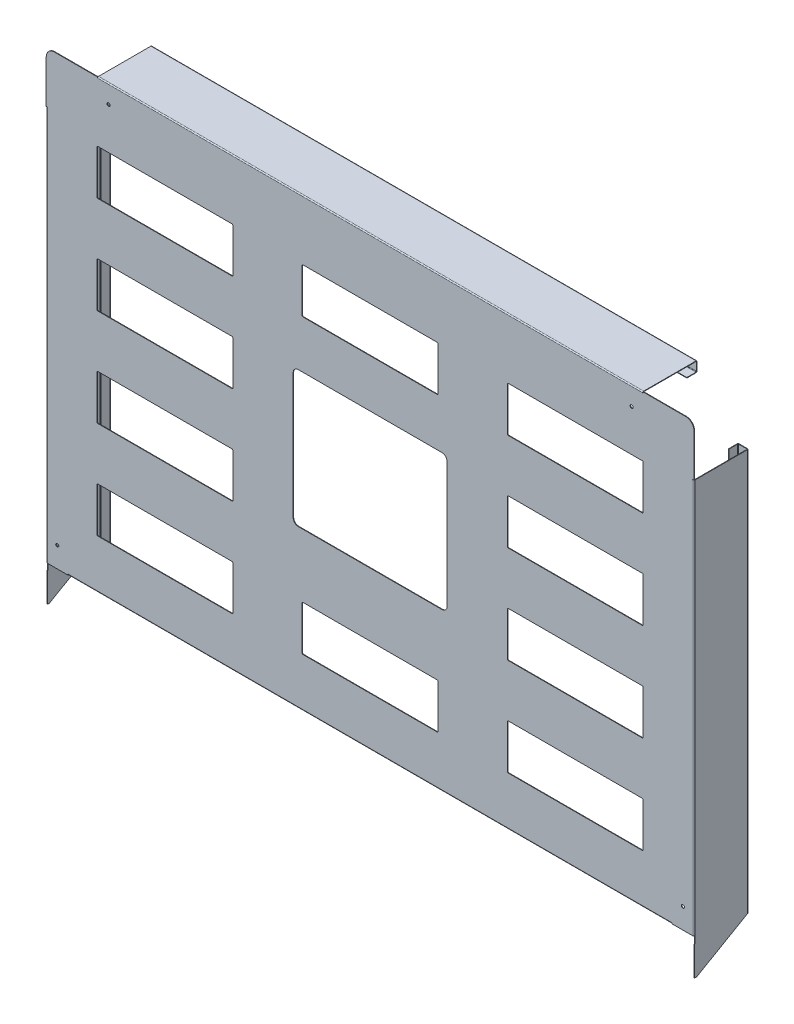
SolidWorks part; units mm, degrees
note: The reader was unsure of these and kept them because the rebuilt part matched: flange length of "Edge-Flange1", "Edge-Flange2", "Edge-Flange3", "Edge-Flange4", "Edge-Flange5", "Edge-Flange6", "Edge-Flange7".
ref_plane "Front Plane" through (0, 0, 0) normal (0, 0, 1) x (1, 0, 0)
ref_plane "Top Plane" through (0, 0, 0) normal (0, 1, 0) x (1, 0, 0)
ref_plane "Right Plane" through (0, 0, 0) normal (1, 0, 0) x (0, 0, -1)
sketch "Sketch1" plane through (0, 0, 0) normal (0, 0, 1) x (1, 0, 0)
  line L1 (0, 0) -> (1263, 0)
  line L2 (0, 0) -> (0, 854)
  line L3 (16, 870) -> (1247, 870)
  line L4 (1263, 0) -> (1263, 854)
  arc A0 (1247, 870) -> (1263, 854) centre (1247, 854) cw
  arc A1 (0, 854) -> (16, 870) centre (16, 854) cw
  dimension "D3" = 16
  dimension "D1" = 1263
  dimension "D2" = 870
base flange "Base-Flange1" sketch "Sketch1" thickness 1 reverse thickness direction no parameters "D1"=1
edge flange "Edge-Flange1" sketch "Sketch8" flange angle 90 flange length 18 flange position material inside bend radius 1 thickness 1 relief rectangular parameters "D6"=10
sketch "Sketch8" plane through (0, 0, -1) normal (0, -1, 0) x (-1, 0, 0)
  line L0 (0, 0) -> (-1263, 0) construction
  line L1 (-43, 0) -> (-1220, 0)
  line L2 (-1220, 0) -> (-1220, 18)
  line L3 (-1220, 18) -> (-43, 18)
  line L4 (-43, 18) -> (-43, 0)
  line L5 (0, 0) -> (0, -1) construction
  line L6 (-1263, 0) -> (-1263, -1) construction
  circle A0 centre (-82, 9) radius 2.75
  circle A1 centre (-262, 9) radius 2.75
  circle A2 centre (-442, 9) radius 2.75
  circle A3 centre (-622, 9) radius 2.75
  circle A4 centre (-802, 9) radius 2.75
  circle A5 centre (-982, 9) radius 2.75
  circle A6 centre (-1162, 9) radius 2.75
  point P6 (-43, 9)
  dimension "D1" = 5.5
  dimension "D2" = 39
  dimension "D4" = 43
  dimension "D5" = 43
  dimension "D3" = 7
bend "EdgeBend1" bend radius 1 bend angle 90 parameters "D5"=1
sketch "Sketch9" plane through (0, 0, 0) normal (0, 0, 1) x (1, 0, 0)
  line L0 (1263, 0) -> (1263, 854) construction
  line L1 (1162, 753) -> (901, 753)
  line L2 (1164, 751) -> (1164, 667)
  line L3 (1162, 665) -> (901, 665)
  line L4 (899, 751) -> (899, 667)
  line L5 (1247, 870) -> (16, 870) construction
  line L6 (764, 751) -> (764, 667)
  line L7 (762, 753) -> (501, 753)
  line L8 (762, 665) -> (501, 665)
  line L9 (499, 751) -> (499, 667)
  line L10 (364, 751) -> (364, 667)
  line L11 (362, 753) -> (101, 753)
  line L12 (362, 665) -> (101, 665)
  line L13 (99, 751) -> (99, 667)
  line L18 (364, 561) -> (364, 477)
  line L19 (362, 563) -> (101, 563)
  line L20 (362, 475) -> (101, 475)
  line L21 (99, 561) -> (99, 477)
  line L26 (364, 371) -> (364, 287)
  line L27 (362, 373) -> (101, 373)
  line L28 (362, 285) -> (101, 285)
  line L29 (99, 371) -> (99, 287)
  line L30 (764, 181) -> (764, 97)
  line L31 (762, 183) -> (501, 183)
  line L32 (762, 95) -> (501, 95)
  line L33 (499, 181) -> (499, 97)
  line L34 (364, 181) -> (364, 97)
  line L35 (362, 183) -> (101, 183)
  line L36 (362, 95) -> (101, 95)
  line L37 (99, 181) -> (99, 97)
  line L38 (1164, 561) -> (1164, 477)
  line L39 (1162, 563) -> (901, 563)
  line L40 (1162, 475) -> (901, 475)
  line L41 (899, 561) -> (899, 477)
  line L42 (1164, 371) -> (1164, 287)
  line L43 (1162, 373) -> (901, 373)
  line L44 (1162, 285) -> (901, 285)
  line L45 (899, 371) -> (899, 287)
  line L46 (1164, 181) -> (1164, 97)
  line L47 (1162, 183) -> (901, 183)
  line L48 (1162, 95) -> (901, 95)
  line L49 (899, 181) -> (899, 97)
  line L50 (764, 371) -> (764, 287) [skipped]
  line L51 (764, 561) -> (764, 477) [skipped]
  line L52 (762, 563) -> (501, 563) [skipped]
  line L53 (762, 475) -> (501, 475) [skipped]
  line L54 (499, 561) -> (499, 477) [skipped]
  line L55 (762, 373) -> (501, 373) [skipped]
  line L56 (762, 285) -> (501, 285) [skipped]
  line L57 (499, 371) -> (499, 287) [skipped]
  arc A0 (1164, 667) -> (1162, 665) centre (1162, 667) cw
  arc A1 (901, 665) -> (899, 667) centre (901, 667) cw
  arc A2 (901, 753) -> (899, 751) centre (901, 751) ccw
  arc A3 (1162, 753) -> (1164, 751) centre (1162, 751) cw
  arc A4 (762, 753) -> (764, 751) centre (762, 751) cw
  arc A5 (764, 667) -> (762, 665) centre (762, 667) cw
  arc A6 (501, 665) -> (499, 667) centre (501, 667) cw
  arc A7 (501, 753) -> (499, 751) centre (501, 751) ccw
  arc A8 (362, 753) -> (364, 751) centre (362, 751) cw
  arc A9 (364, 667) -> (362, 665) centre (362, 667) cw
  arc A10 (101, 665) -> (99, 667) centre (101, 667) cw
  arc A11 (101, 753) -> (99, 751) centre (101, 751) ccw
  arc A16 (362, 563) -> (364, 561) centre (362, 561) cw
  arc A17 (364, 477) -> (362, 475) centre (362, 477) cw
  arc A18 (101, 475) -> (99, 477) centre (101, 477) cw
  arc A19 (101, 563) -> (99, 561) centre (101, 561) ccw
  arc A24 (362, 373) -> (364, 371) centre (362, 371) cw
  arc A25 (364, 287) -> (362, 285) centre (362, 287) cw
  arc A26 (101, 285) -> (99, 287) centre (101, 287) cw
  arc A27 (101, 373) -> (99, 371) centre (101, 371) ccw
  arc A28 (762, 183) -> (764, 181) centre (762, 181) cw
  arc A29 (764, 97) -> (762, 95) centre (762, 97) cw
  arc A30 (501, 95) -> (499, 97) centre (501, 97) cw
  arc A31 (501, 183) -> (499, 181) centre (501, 181) ccw
  arc A32 (362, 183) -> (364, 181) centre (362, 181) cw
  arc A33 (364, 97) -> (362, 95) centre (362, 97) cw
  arc A34 (101, 95) -> (99, 97) centre (101, 97) cw
  arc A35 (101, 183) -> (99, 181) centre (101, 181) ccw
  arc A36 (1162, 563) -> (1164, 561) centre (1162, 561) cw
  arc A37 (1164, 477) -> (1162, 475) centre (1162, 477) cw
  arc A38 (901, 475) -> (899, 477) centre (901, 477) cw
  arc A39 (901, 563) -> (899, 561) centre (901, 561) ccw
  arc A40 (1162, 373) -> (1164, 371) centre (1162, 371) cw
  arc A41 (1164, 287) -> (1162, 285) centre (1162, 287) cw
  arc A42 (901, 285) -> (899, 287) centre (901, 287) cw
  arc A43 (901, 373) -> (899, 371) centre (901, 371) ccw
  arc A44 (1162, 183) -> (1164, 181) centre (1162, 181) cw
  arc A45 (1164, 97) -> (1162, 95) centre (1162, 97) cw
  arc A46 (901, 95) -> (899, 97) centre (901, 97) cw
  arc A47 (901, 183) -> (899, 181) centre (901, 181) ccw
  arc A48 (764, 477) -> (762, 475) centre (762, 477) cw [skipped]
  arc A49 (501, 475) -> (499, 477) centre (501, 477) cw [skipped]
  arc A50 (762, 373) -> (764, 371) centre (762, 371) cw [skipped]
  arc A51 (764, 287) -> (762, 285) centre (762, 287) cw [skipped]
  arc A52 (501, 285) -> (499, 287) centre (501, 287) cw [skipped]
  arc A53 (501, 373) -> (499, 371) centre (501, 371) ccw [skipped]
  arc A54 (762, 563) -> (764, 561) centre (762, 561) cw [skipped]
  arc A55 (501, 563) -> (499, 561) centre (501, 561) ccw [skipped]
  dimension "D5" = 2
  dimension "D1" = 99
  dimension "D2" = 265
  dimension "D3" = 88
  dimension "D4" = 117
  dimension "D6" = 3
  dimension "D7" = 4
extrude "Cut-Extrude1" cut sketch "Sketch9" against normal blind 10 normal cut yes
sketch "Sketch10" plane through (0, 0, 0) normal (0, 0, 1) x (1, 0, 0)
  line L1 (491.5, 306.5) -> (771.5, 306.5)
  line L2 (481.5, 316.5) -> (481.5, 561.5)
  line L3 (491.5, 571.5) -> (771.5, 571.5)
  line L4 (781.5, 316.5) -> (781.5, 561.5)
  line L8 (1247, 870) -> (16, 870) construction
  arc A0 (491.5, 306.5) -> (481.5, 316.5) centre (491.5, 316.5) cw
  arc A1 (771.5, 306.5) -> (781.5, 316.5) centre (771.5, 316.5) ccw
  arc A2 (481.5, 561.5) -> (491.5, 571.5) centre (491.5, 561.5) cw
  arc A3 (771.5, 571.5) -> (781.5, 561.5) centre (771.5, 561.5) cw
  point P8 (631.5, 571.5)
  point P9 (631.5, 870)
  dimension "D5" = 10
  dimension "D1" = 300
  dimension "D2" = 265
  dimension "D3" = 298.5
extrude "Cut-Extrude2" cut sketch "Sketch10" against normal blind 10 normal cut yes
sketch "Sketch11" plane through (0, 0, -1) normal (0, 0, -1) x (-1, 0, 0)
  line L0 (-762.2929, 578.3623) -> (-474.7071, 578.3623) construction
  line L1 (-762.2929, 578.3623) -> (-474.7071, 578.3623) construction
  line L2 (-455.5, 559.4244) -> (-455.5, 302.3841) construction
  line L3 (-474.7071, 282.858) -> (-762.2929, 282.858) construction
  line L4 (-781.5, 302.8243) -> (-781.5, 559.4244) construction
  line L5 (-781.5, 302.3841) -> (-781.5, 559.4244) construction
  ellipse E0 centre (-474.7071, 576.3964) end of major axis (-472.7071, 576.3964) minor radius 1.9659 (-472.7071, 576.3964) -> (-474.7071, 578.3623) ccw construction
edge flange "Edge-Flange2" sketch "Sketch14" flange angle 90 flange length 104 flange position material inside bend radius 1 thickness 1 relief rectangular parameters "D6"=10
sketch "Sketch14" plane through (0, 870, -1) normal (0, 1, 0) x (1, 0, 0)
  line L0 (1247, 0) -> (16, 0) construction
  line L1 (1163, 0) -> (100, 0)
  line L2 (100, 0) -> (100, 103)
  line L3 (100, 103) -> (1163, 103)
  line L4 (1163, 103) -> (1163, 0)
  line L5 (1263, 0) -> (1263, -1) construction
  line L6 (0, 0) -> (0, -1) construction
  dimension "D1" = 100
  dimension "D2" = 100
  dimension "D3" = 103
bend "EdgeBend2" bend radius 1 bend angle 90 parameters "D5"=2
edge flange "Edge-Flange3" sketch "Sketch19" flange angle 90 flange length 104 flange position material inside bend radius 1 thickness 1 relief rectangular parameters "D6"=10
sketch "Sketch19" plane through (1263, 0, -1) normal (1, 0, 0) x (0, -1, 0)
  line L0 (0, 0) -> (-854, 0) construction
  line L1 (13.7, 0) -> (-770, 0)
  line L2 (-770, 0) -> (-770, 103)
  line L3 (-770, 103) -> (13.7, 103)
  line L4 (13.7, 103) -> (13.7, 0)
  line L5 (-870, 1) -> (-870, 103) construction
  dimension "D1" = 100
  dimension "D2" = 103
  dimension "D3" = 13.7
bend "EdgeBend3" bend radius 1 bend angle 90 parameters "D5"=3
edge flange "Edge-Flange4" sketch "Sketch22" flange angle 90 flange length 18 flange position bend outside bend radius 1 thickness 1 relief rectangular parameters "D6"=10
sketch "Sketch22" plane through (0, 869, -104) normal (0, 0, -1) x (1, 0, 0)
  line L0 (1163, 0) -> (100, 0) construction
  line L1 (1163, 0) -> (100, 0)
  line L2 (100, 0) -> (100, 17)
  line L3 (100, 17) -> (1163, 17)
  line L4 (1163, 17) -> (1163, 0)
bend "EdgeBend4" bend radius 1 bend angle 90 parameters "D5"=4
edge flange "Edge-Flange5" sketch "Sketch25" flange angle 90 flange length 20 flange position bend outside bend radius 1 thickness 1 relief rectangular parameters "D6"=10
sketch "Sketch25" plane through (0, 852, -105) normal (0, 1, 0) x (-1, 0, 0)
  line L2 (-1163, 0) -> (-1163, 19)
  line L3 (-1163, 19) -> (-100, 19)
  line L4 (-100, 19) -> (-100, 0)
  line L5 (-100, 0) -> (-1163, 0) construction
  line L6 (-100, 0) -> (-1163, 0)
bend "EdgeBend5" bend radius 1 bend angle 90 parameters "D5"=5
edge flange "Edge-Flange6" sketch "Sketch28" flange angle 90 flange length 18 flange position bend outside bend radius 1 thickness 1 relief rectangular parameters "D6"=10
sketch "Sketch28" plane through (1262, 0, -104) normal (0, 0, -1) x (0, -1, 0)
  line L0 (13.7, 0) -> (-770, 0) construction
  line L1 (13.7, 0) -> (-770, 0)
  line L2 (-770, 0) -> (-770, 17)
  line L3 (-770, 17) -> (13.7, 17)
  line L4 (13.7, 17) -> (13.7, 0)
bend "EdgeBend6" bend radius 1 bend angle 90 parameters "D5"=6
edge flange "Edge-Flange7" sketch "Sketch31" flange angle 90 flange length 19 flange position bend outside bend radius 1 thickness 1 relief rectangular parameters "D6"=10
sketch "Sketch31" plane through (1245, 0, -105) normal (1, 0, 0) x (0, 1, 0)
  line L2 (-13.7, 0) -> (-13.7, 18)
  line L3 (-13.7, 18) -> (770, 18)
  line L4 (770, 18) -> (770, 0)
  line L9 (770, 0) -> (-13.7, 0) construction
  line L10 (770, 0) -> (-13.7, 0)
bend "EdgeBend7" bend radius 1 bend angle 90 parameters "D5"=7
ref_plane "Plane1" through (631.5, 0, 0) normal (1, 0, 0) x (0, 0, -1)
mirror "Mirror1" about plane through (631.5, 0, 0) normal (1, 0, 0) of "Edge-Flange3", "Edge-Flange6", "Edge-Flange7"
bend "MirrorBend1" bend radius 1 bend angle 90 parameters "D5"=8
bend "MirrorBend2" bend radius 1 bend angle 90 parameters "D5"=9
bend "MirrorBend3" bend radius 1 bend angle 90 parameters "D5"=10
sketch "Sketch32" plane through (1263, 0, 0) normal (1, 0, 0) x (0, 0, -1)
  line L1 (5.5055, -70.5658) -> (104, -13.7)
  line L2 (104, -13.7) -> (1, -13.7)
  line L4 (1, -13.7) -> (1, -70.1998)
  line L5 (1.5, -70.6998) -> (5.0055, -70.6998)
  line L7 (2, -13.7) -> (2, 0) construction
  arc A0 (5.0055, -70.6998) -> (5.5055, -70.5658) centre (5.0055, -69.6998) ccw
  arc A1 (1, -70.1998) -> (1.5, -70.6998) centre (1.5, -70.1998) ccw
  point P12 (5.2734, -70.6998)
  dimension "D4" = 1
  dimension "D5" = 0.5
  dimension "D1" = 30
  dimension "D2" = 1
base flange "Tab1" sketch "Sketch32" thickness 1 reverse thickness direction no parameters "D1"=1
ref_plane "Plane2" through (631.5, 0, 0) normal (1, 0, 0) x (0, 0, -1)
mirror "Mirror2" about plane through (631.5, 0, 0) normal (1, 0, 0) of "Tab1"
sketch "Sketch33" plane through (0, 0, 0) normal (0, 0, 1) x (1, 0, 0)
  line L0 (631.5, 868) -> (631.5, 781.3325) construction
  line L1 (1163, 868) -> (100, 868) construction
  line L2 (99.5, 870) -> (16, 870) construction
  line L3 (0, 854) -> (0, 770.5) construction
  line L4 (2, 0) -> (42.5, 0) construction
  line L5 (0, 770) -> (0, 0) construction
  circle A0 centre (121.5, 834) radius 3
  circle A1 centre (1141.5, 834) radius 3
  circle A2 centre (21.5, 40) radius 3
  circle A3 centre (1241.5, 40) radius 3
  dimension "D1" = 6
  dimension "D3" = 121.5
  dimension "D4" = 6
  dimension "D5" = 40
  dimension "D6" = 21.5
  dimension "D2" = 36
extrude "Cut-Extrude3" cut sketch "Sketch33" against normal blind 10 normal cut yes
sketch "Bend-Lines1" [suppressed] plane through (0, 0, 0) normal (0, 1, 0) x (1, 0, 0)
sketch "Bounding-Box1" [suppressed] plane through (0, 0, 0) normal (0, 1, 0) x (1, 0, 0)
sheet metal parameters "Sheet-Metal1" thickness 1 parameters "D1"=2
flat pattern "Flat-Pattern1" [suppressed]
sketch "Bend-Lines2" plane through (0, 0, 0) normal (0, 1, 0) x (1, 0, 0)
sketch3d "Bounding-Box2" [suppressed]
  line L0 (15, 15, 0) -> (-1227, 15, 0) construction
  line L1 (15, -935, 0) -> (-1227, -935, 0) construction
  line L2 (15, 15, 0) -> (15, -935, 0) construction
  line L3 (-1227, 15, 0) -> (-1227, -935, 0) construction
sheet metal parameters "Sheet-Metal2" thickness 1 parameters "D1"=2
flat pattern "Flat-Pattern1"
sketch "Bend-Lines2" plane through (0, 0, 0) normal (0, 0, 1) x (1, 0, 0)
  line L0 (0, 0.8219) -> (1242, 0.8219) construction
  line L1 (0, 0.8219) -> (1242, 0.8219) construction
sketch3d "Bounding-Box2" [suppressed]
  line L0 (-15, 15, 0) -> (1227, 15, 0) construction
  line L1 (-15, -946.3562, 0) -> (1227, -946.3562, 0) construction
  line L2 (-15, 15, 0) -> (-15, -946.3562, 0) construction
  line L3 (1227, 15, 0) -> (1227, -946.3562, 0) construction
bend of the flat pattern "Flatten-<EdgeBend1>1"
sheet metal parameters "Sheet-Metal3" thickness 1 parameters "D1"=2
flat pattern "Flat-Pattern1"
sketch "Bend-Lines2" plane through (0, 0, 0) normal (0, 0, 1) x (1, 0, 0)
  line L0 (0, 0.8219) -> (1244, 0.8219) construction
  line L1 (0, 0.8219) -> (1244, 0.8219) construction
sketch3d "Bounding-Box2" [suppressed]
  line L0 (-16, 16, 0) -> (1228, 16, 0) construction
  line L1 (-16, -945.3562, 0) -> (1228, -945.3562, 0) construction
  line L2 (-16, 16, 0) -> (-16, -945.3562, 0) construction
  line L3 (1228, 16, 0) -> (1228, -945.3562, 0) construction
bend of the flat pattern "Flatten-<EdgeBend1>1"
sheet metal parameters "Sheet-Metal4" thickness 1 parameters "D1"=2
flat pattern "Flat-Pattern1"
sketch "Bend-Lines2" plane through (0, 0, 0) normal (0, 0, 1) x (1, 0, 0)
  line L0 (43, 0.8219) -> (1201, 0.8219) construction
  line L1 (43, 0.8219) -> (1201, 0.8219) construction
sketch3d "Bounding-Box2" [suppressed]
  line L0 (-16, 16, 0) -> (1228, 16, 0) construction
  line L1 (-16, -861.3562, 0) -> (1228, -861.3562, 0) construction
  line L2 (-16, 16, 0) -> (-16, -861.3562, 0) construction
  line L3 (1228, 16, 0) -> (1228, -861.3562, 0) construction
bend of the flat pattern "Flatten-<EdgeBend1>1"
sheet metal parameters "Sheet-Metal5" thickness 1 parameters "D1"=2
flat pattern "Flat-Pattern1"
sketch "Bend-Lines2" plane through (0, 0, 0) normal (0, 0, 1) x (1, 0, 0)
  line L0 (43, 0.8219) -> (1201, 0.8219) construction
  line L1 (43, 0.8219) -> (1201, 0.8219) construction
  line L2 (1144, 861.1781) -> (100, 861.1781) construction
  line L3 (1144, 861.1781) -> (100, 861.1781) construction
sketch3d "Bounding-Box2" [suppressed]
  line L0 (-16, 117.3562, 0) -> (1228, 117.3562, 0) construction
  line L1 (-16, -861.3562, 0) -> (1228, -861.3562, 0) construction
  line L2 (-16, 117.3562, 0) -> (-16, -861.3562, 0) construction
  line L3 (1228, 117.3562, 0) -> (1228, -861.3562, 0) construction
bend of the flat pattern "Flatten-<EdgeBend1>1"
bend of the flat pattern "Flatten-<EdgeBend2>1"
sheet metal parameters "Sheet-Metal6" thickness 1 parameters "D1"=2
flat pattern "Flat-Pattern1"
sketch "Bend-Lines2" plane through (0, 0, 0) normal (0, 0, 1) x (1, 0, 0)
  line L0 (43, 0.8219) -> (1201, 0.8219) construction
  line L1 (43, 0.8219) -> (1201, 0.8219) construction
  line L2 (1144, 861.1781) -> (100, 861.1781) construction
  line L3 (1144, 861.1781) -> (100, 861.1781) construction
  line L4 (1245.1781, 0) -> (1245.1781, 762) construction
  line L5 (1245.1781, 0) -> (1245.1781, 762) construction
sketch3d "Bounding-Box2" [suppressed]
  line L0 (-16, 117.3562, 0) -> (1329.3562, 117.3562, 0) construction
  line L1 (-16, -861.3562, 0) -> (1329.3562, -861.3562, 0) construction
  line L2 (-16, 117.3562, 0) -> (-16, -861.3562, 0) construction
  line L3 (1329.3562, 117.3562, 0) -> (1329.3562, -861.3562, 0) construction
bend of the flat pattern "Flatten-<EdgeBend1>1"
bend of the flat pattern "Flatten-<EdgeBend2>1"
bend of the flat pattern "Flatten-<EdgeBend3>1"
sheet metal parameters "Sheet-Metal7" thickness 1 parameters "D1"=2
flat pattern "Flat-Pattern1"
sketch "Bend-Lines2" plane through (0, 0, 0) normal (0, 0, 1) x (1, 0, 0)
  line L0 (43, 0.8219) -> (1201, 0.8219) construction
  line L1 (43, 0.8219) -> (1201, 0.8219) construction
  line L2 (1144, 861.1781) -> (100, 861.1781) construction
  line L3 (1144, 861.1781) -> (100, 861.1781) construction
  line L4 (1245.1781, 0) -> (1245.1781, 762) construction
  line L5 (1245.1781, 0) -> (1245.1781, 762) construction
  line L6 (1144, 962.5343) -> (100, 962.5343) construction
  line L7 (1144, 962.5343) -> (100, 962.5343) construction
sketch3d "Bounding-Box2" [suppressed]
  line L0 (-16, 135.7124, 0) -> (1329.3562, 135.7124, 0) construction
  line L1 (-16, -861.3562, 0) -> (1329.3562, -861.3562, 0) construction
  line L2 (-16, 135.7124, 0) -> (-16, -861.3562, 0) construction
  line L3 (1329.3562, 135.7124, 0) -> (1329.3562, -861.3562, 0) construction
bend of the flat pattern "Flatten-<EdgeBend1>1"
bend of the flat pattern "Flatten-<EdgeBend2>1"
bend of the flat pattern "Flatten-<EdgeBend3>1"
bend of the flat pattern "Flatten-<EdgeBend4>1"
sheet metal parameters "Sheet-Metal8" thickness 1 parameters "D1"=2
flat pattern "Flat-Pattern1"
sketch "Bend-Lines2" plane through (0, 0, 0) normal (0, 0, 1) x (1, 0, 0)
  line L0 (43, 0.8219) -> (1201, 0.8219) construction
  line L1 (43, 0.8219) -> (1201, 0.8219) construction
  line L2 (1144, 861.1781) -> (100, 861.1781) construction
  line L3 (1144, 861.1781) -> (100, 861.1781) construction
  line L4 (1245.1781, 0) -> (1245.1781, 762) construction
  line L5 (1245.1781, 0) -> (1245.1781, 762) construction
  line L6 (1144, 962.5343) -> (100, 962.5343) construction
  line L7 (1144, 962.5343) -> (100, 962.5343) construction
  line L8 (1144, 980.8905) -> (100, 980.8905) construction
  line L9 (1144, 980.8905) -> (100, 980.8905) construction
sketch3d "Bounding-Box2" [suppressed]
  line L0 (-16, 156.0686, 0) -> (1329.3562, 156.0686, 0) construction
  line L1 (-16, -861.3562, 0) -> (1329.3562, -861.3562, 0) construction
  line L2 (-16, 156.0686, 0) -> (-16, -861.3562, 0) construction
  line L3 (1329.3562, 156.0686, 0) -> (1329.3562, -861.3562, 0) construction
bend of the flat pattern "Flatten-<EdgeBend1>1"
bend of the flat pattern "Flatten-<EdgeBend2>1"
bend of the flat pattern "Flatten-<EdgeBend3>1"
bend of the flat pattern "Flatten-<EdgeBend4>1"
bend of the flat pattern "Flatten-<EdgeBend5>1"
sheet metal parameters "Sheet-Metal9" thickness 1 parameters "D1"=2
flat pattern "Flat-Pattern1"
sketch "Bend-Lines2" plane through (0, 0, 0) normal (0, 0, 1) x (1, 0, 0)
  line L0 (43, 0.8219) -> (1201, 0.8219) construction
  line L1 (43, 0.8219) -> (1201, 0.8219) construction
  line L2 (1144, 861.1781) -> (100, 861.1781) construction
  line L3 (1144, 861.1781) -> (100, 861.1781) construction
  line L4 (1245.1781, 0) -> (1245.1781, 762) construction
  line L5 (1245.1781, 0) -> (1245.1781, 762) construction
  line L6 (1144, 962.5343) -> (100, 962.5343) construction
  line L7 (1144, 962.5343) -> (100, 962.5343) construction
  line L8 (1144, 980.8905) -> (100, 980.8905) construction
  line L9 (1144, 980.8905) -> (100, 980.8905) construction
  line L10 (1346.5343, 0) -> (1346.5343, 762) construction
  line L11 (1346.5343, 0) -> (1346.5343, 762) construction
sketch3d "Bounding-Box2" [suppressed]
  line L0 (-16, 156.0686, 0) -> (1347.7124, 156.0686, 0) construction
  line L1 (-16, -861.3562, 0) -> (1347.7124, -861.3562, 0) construction
  line L2 (-16, 156.0686, 0) -> (-16, -861.3562, 0) construction
  line L3 (1347.7124, 156.0686, 0) -> (1347.7124, -861.3562, 0) construction
bend of the flat pattern "Flatten-<EdgeBend1>1"
bend of the flat pattern "Flatten-<EdgeBend2>1"
bend of the flat pattern "Flatten-<EdgeBend3>1"
bend of the flat pattern "Flatten-<EdgeBend4>1"
bend of the flat pattern "Flatten-<EdgeBend5>1"
bend of the flat pattern "Flatten-<EdgeBend6>1"
sheet metal parameters "Sheet-Metal10" thickness 1 parameters "D1"=2
flat pattern "Flat-Pattern1"
sketch "Bend-Lines2" plane through (0, 0, 0) normal (0, 0, 1) x (1, 0, 0)
  line L0 (43, 0.8219) -> (1201, 0.8219) construction
  line L1 (43, 0.8219) -> (1201, 0.8219) construction
  line L2 (1144, 861.1781) -> (100, 861.1781) construction
  line L3 (1144, 861.1781) -> (100, 861.1781) construction
  line L4 (1245.1781, 0) -> (1245.1781, 762) construction
  line L5 (1245.1781, 0) -> (1245.1781, 762) construction
  line L6 (1144, 962.5343) -> (100, 962.5343) construction
  line L7 (1144, 962.5343) -> (100, 962.5343) construction
  line L8 (1144, 980.8905) -> (100, 980.8905) construction
  line L9 (1144, 980.8905) -> (100, 980.8905) construction
  line L10 (1346.5343, 0) -> (1346.5343, 762) construction
  line L11 (1346.5343, 0) -> (1346.5343, 762) construction
  line L12 (1364.8905, 0) -> (1364.8905, 762) construction
  line L13 (1364.8905, 0) -> (1364.8905, 762) construction
sketch3d "Bounding-Box2" [suppressed]
  line L0 (-16, 156.0686, 0) -> (1368.0686, 156.0686, 0) construction
  line L1 (-16, -861.3562, 0) -> (1368.0686, -861.3562, 0) construction
  line L2 (-16, 156.0686, 0) -> (-16, -861.3562, 0) construction
  line L3 (1368.0686, 156.0686, 0) -> (1368.0686, -861.3562, 0) construction
bend of the flat pattern "Flatten-<EdgeBend1>1"
bend of the flat pattern "Flatten-<EdgeBend2>1"
bend of the flat pattern "Flatten-<EdgeBend3>1"
bend of the flat pattern "Flatten-<EdgeBend4>1"
bend of the flat pattern "Flatten-<EdgeBend5>1"
bend of the flat pattern "Flatten-<EdgeBend6>1"
bend of the flat pattern "Flatten-<EdgeBend7>1"
sheet metal parameters "Sheet-Metal11" thickness 1 parameters "D1"=2
flat pattern "Flat-Pattern1"
sketch "Bend-Lines2" plane through (0, 0, 0) normal (0, 0, 1) x (1, 0, 0)
  line L0 (43, 0.8219) -> (1220, 0.8219) construction
  line L1 (43, 0.8219) -> (1220, 0.8219) construction
  line L2 (1163, 869.1781) -> (100, 869.1781) construction
  line L3 (1163, 869.1781) -> (100, 869.1781) construction
  line L4 (1262.1781, 0) -> (1262.1781, 770) construction
  line L5 (1262.1781, 0) -> (1262.1781, 770) construction
  line L6 (1163, 973.5343) -> (100, 973.5343) construction
  line L7 (1163, 973.5343) -> (100, 973.5343) construction
  line L8 (1163, 991.8905) -> (100, 991.8905) construction
  line L9 (1163, 991.8905) -> (100, 991.8905) construction
  line L10 (1366.5343, 0) -> (1366.5343, 770) construction
  line L11 (1366.5343, 0) -> (1366.5343, 770) construction
  line L12 (1384.8905, 0) -> (1384.8905, 770) construction
  line L13 (1384.8905, 0) -> (1384.8905, 770) construction
  line L14 (-121.8905, 770) -> (-121.8905, 0) construction
  line L15 (-103.5343, 770) -> (-103.5343, 0) construction
  line L16 (0.8219, 770) -> (0.8219, 0) construction
  line L17 (-121.8905, 770) -> (-121.8905, 0) construction
  line L18 (-103.5343, 770) -> (-103.5343, 0) construction
  line L19 (0.8219, 770) -> (0.8219, 0) construction
sketch3d "Bounding-Box2" [suppressed]
  line L0 (-157.0686, -871.3562, 0) -> (1388.0686, -871.3562, 0) construction
  line L1 (-157.0686, 157.0686, 0) -> (1388.0686, 157.0686, 0) construction
  line L2 (-157.0686, -871.3562, 0) -> (-157.0686, 157.0686, 0) construction
  line L3 (1388.0686, -871.3562, 0) -> (1388.0686, 157.0686, 0) construction
bend of the flat pattern "Flatten-<EdgeBend1>1"
bend of the flat pattern "Flatten-<EdgeBend2>1"
bend of the flat pattern "Flatten-<EdgeBend3>1"
bend of the flat pattern "Flatten-<EdgeBend4>1"
bend of the flat pattern "Flatten-<EdgeBend5>1"
bend of the flat pattern "Flatten-<EdgeBend6>1"
bend of the flat pattern "Flatten-<EdgeBend7>1"
bend of the flat pattern "Flatten-<MirrorBend1>1"
bend of the flat pattern "Flatten-<MirrorBend2>1"
bend of the flat pattern "Flatten-<MirrorBend3>1"
sheet metal parameters "Sheet-Metal12" thickness 1 parameters "D1"=2
flat pattern "Flat-Pattern12"
sketch "Bend-Lines3" plane through (0, 0, 0) normal (0, 0, 1) x (1, 0, 0)
  line L0 (-121.8905, 770) -> (-121.8905, 0) construction
  line L1 (-103.5343, 770) -> (-103.5343, 0) construction
  line L2 (0.8219, 770) -> (0.8219, 0) construction
  line L3 (1384.8905, 0) -> (1384.8905, 770) construction
  line L4 (1366.5343, 0) -> (1366.5343, 770) construction
  line L5 (1163, 991.8905) -> (100, 991.8905) construction
  line L6 (1163, 973.5343) -> (100, 973.5343) construction
  line L7 (1262.1781, 0) -> (1262.1781, 770) construction
  line L8 (1163, 869.1781) -> (100, 869.1781) construction
  line L9 (43, 0.8219) -> (1220, 0.8219) construction
  line L10 (-121.8905, 770) -> (-121.8905, 0) construction
  line L11 (-103.5343, 770) -> (-103.5343, 0) construction
  line L12 (0.8219, 770) -> (0.8219, 0) construction
  line L13 (1384.8905, 0) -> (1384.8905, 770) construction
  line L14 (1366.5343, 0) -> (1366.5343, 770) construction
  line L15 (1163, 991.8905) -> (100, 991.8905) construction
  line L16 (1163, 973.5343) -> (100, 973.5343) construction
  line L17 (1262.1781, 0) -> (1262.1781, 770) construction
  line L18 (1163, 869.1781) -> (100, 869.1781) construction
  line L19 (43, 0.8219) -> (1220, 0.8219) construction
sketch3d "Bounding-Box3" [suppressed]
  line L0 (-157.0686, -929, 0) -> (1388.0686, -929, 0) construction
  line L1 (-157.0686, 157.0686, 0) -> (1388.0686, 157.0686, 0) construction
  line L2 (-157.0686, -929, 0) -> (-157.0686, 157.0686, 0) construction
  line L3 (1388.0686, -929, 0) -> (1388.0686, 157.0686, 0) construction
bend of the flat pattern "Flatten-<MirrorBend3>2"
bend of the flat pattern "Flatten-<MirrorBend2>2"
bend of the flat pattern "Flatten-<MirrorBend1>2"
bend of the flat pattern "Flatten-<EdgeBend7>2"
bend of the flat pattern "Flatten-<EdgeBend6>2"
bend of the flat pattern "Flatten-<EdgeBend5>2"
bend of the flat pattern "Flatten-<EdgeBend4>2"
bend of the flat pattern "Flatten-<EdgeBend3>2"
bend of the flat pattern "Flatten-<EdgeBend2>2"
bend of the flat pattern "Flatten-<EdgeBend1>2"
sheet metal parameters "Sheet-Metal13" thickness 1 parameters "D1"=2
flat pattern "Flat-Pattern12"
sketch "Bend-Lines3" plane through (0, 0, 0) normal (0, 0, 1) x (1, 0, 0)
  line L0 (-121.8905, 770) -> (-121.8905, -13.7) construction
  line L1 (-103.5343, 770) -> (-103.5343, -13.7) construction
  line L2 (0.8219, 770) -> (0.8219, 0) construction
  line L3 (1384.8905, -13.7) -> (1384.8905, 770) construction
  line L4 (1366.5343, -13.7) -> (1366.5343, 770) construction
  line L5 (1163, 991.8905) -> (100, 991.8905) construction
  line L6 (1163, 973.5343) -> (100, 973.5343) construction
  line L7 (1262.1781, 0) -> (1262.1781, 770) construction
  line L8 (1163, 869.1781) -> (100, 869.1781) construction
  line L9 (43, 0.8219) -> (1220, 0.8219) construction
  line L10 (-121.8905, 770) -> (-121.8905, -13.7) construction
  line L11 (-103.5343, 770) -> (-103.5343, -13.7) construction
  line L12 (0.8219, 770) -> (0.8219, 0) construction
  line L13 (1384.8905, -13.7) -> (1384.8905, 770) construction
  line L14 (1366.5343, -13.7) -> (1366.5343, 770) construction
  line L15 (1163, 991.8905) -> (100, 991.8905) construction
  line L16 (1163, 973.5343) -> (100, 973.5343) construction
  line L17 (1262.1781, 0) -> (1262.1781, 770) construction
  line L18 (1163, 869.1781) -> (100, 869.1781) construction
  line L19 (43, 0.8219) -> (1220, 0.8219) construction
sketch3d "Bounding-Box3" [suppressed]
  line L0 (-156.0686, -924.6998, 0) -> (1387.0686, -924.6998, 0) construction
  line L1 (-156.0686, 157.0686, 0) -> (1387.0686, 157.0686, 0) construction
  line L2 (-156.0686, -924.6998, 0) -> (-156.0686, 157.0686, 0) construction
  line L3 (1387.0686, -924.6998, 0) -> (1387.0686, 157.0686, 0) construction
bend of the flat pattern "Flatten-<MirrorBend3>2"
bend of the flat pattern "Flatten-<MirrorBend2>2"
bend of the flat pattern "Flatten-<MirrorBend1>2"
bend of the flat pattern "Flatten-<EdgeBend7>2"
bend of the flat pattern "Flatten-<EdgeBend6>2"
bend of the flat pattern "Flatten-<EdgeBend5>2"
bend of the flat pattern "Flatten-<EdgeBend4>2"
bend of the flat pattern "Flatten-<EdgeBend3>2"
bend of the flat pattern "Flatten-<EdgeBend2>2"
bend of the flat pattern "Flatten-<EdgeBend1>2"
sheet metal parameters "Sheet-Metal14" thickness 1 parameters "D1"=2
flat pattern "Flat-Pattern12"
sketch "Bend-Lines3" plane through (0, 0, 0) normal (0, 0, 1) x (1, 0, 0)
  line L0 (-121.8905, 770) -> (-121.8905, -13.7) construction
  line L1 (-103.5343, 770) -> (-103.5343, -13.7) construction
  line L2 (0.8219, 770) -> (0.8219, 0) construction
  line L3 (1384.8905, -13.7) -> (1384.8905, 770) construction
  line L4 (1366.5343, -13.7) -> (1366.5343, 770) construction
  line L5 (1163, 991.8905) -> (100, 991.8905) construction
  line L6 (1163, 973.5343) -> (100, 973.5343) construction
  line L7 (1262.1781, 0) -> (1262.1781, 770) construction
  line L8 (1163, 869.1781) -> (100, 869.1781) construction
  line L9 (43, 0.8219) -> (1220, 0.8219) construction
  line L10 (-121.8905, 770) -> (-121.8905, -13.7) construction
  line L11 (-103.5343, 770) -> (-103.5343, -13.7) construction
  line L12 (0.8219, 770) -> (0.8219, 0) construction
  line L13 (1384.8905, -13.7) -> (1384.8905, 770) construction
  line L14 (1366.5343, -13.7) -> (1366.5343, 770) construction
  line L15 (1163, 991.8905) -> (100, 991.8905) construction
  line L16 (1163, 973.5343) -> (100, 973.5343) construction
  line L17 (1262.1781, 0) -> (1262.1781, 770) construction
  line L18 (1163, 869.1781) -> (100, 869.1781) construction
  line L19 (43, 0.8219) -> (1220, 0.8219) construction
sketch3d "Bounding-Box3" [suppressed]
  line L0 (-156.0686, -924.6998, 0) -> (1387.0686, -924.6998, 0) construction
  line L1 (-156.0686, 157.0686, 0) -> (1387.0686, 157.0686, 0) construction
  line L2 (-156.0686, -924.6998, 0) -> (-156.0686, 157.0686, 0) construction
  line L3 (1387.0686, -924.6998, 0) -> (1387.0686, 157.0686, 0) construction
bend of the flat pattern "Flatten-<MirrorBend3>2"
bend of the flat pattern "Flatten-<MirrorBend2>2"
bend of the flat pattern "Flatten-<MirrorBend1>2"
bend of the flat pattern "Flatten-<EdgeBend7>2"
bend of the flat pattern "Flatten-<EdgeBend6>2"
bend of the flat pattern "Flatten-<EdgeBend5>2"
bend of the flat pattern "Flatten-<EdgeBend4>2"
bend of the flat pattern "Flatten-<EdgeBend3>2"
bend of the flat pattern "Flatten-<EdgeBend2>2"
bend of the flat pattern "Flatten-<EdgeBend1>2"
equation "\"D5@Sketch8\"=\"D4@Sketch8\""
equation "\"D2@Sketch14\" = \"D1@Sketch14\""
